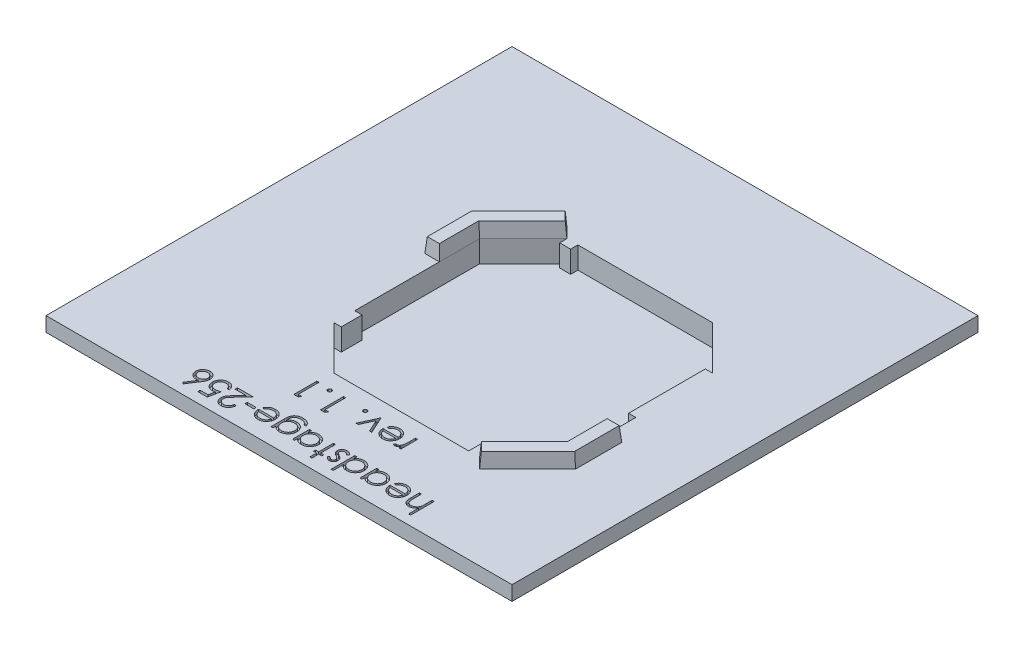
SolidWorks part; units mm, degrees
ref_plane "Front Plane" through (0, 0, 0) normal (0, 0, 1) x (1, 0, 0)
ref_plane "Top Plane" through (0, 0, 0) normal (0, 1, 0) x (1, 0, 0)
ref_plane "Right Plane" through (0, 0, 0) normal (1, 0, 0) x (0, 0, -1)
sketch "Sketch1" plane through (0, 0, 0) normal (0, 1, 0) x (1, 0, 0)
  line L1 (-32, 32) -> (32, 32)
  line L2 (-32, 32) -> (-32, -32)
  line L3 (-32, -32) -> (32, -32)
  line L4 (32, 32) -> (32, -32)
  line L5 (-32, 32) -> (32, -32) construction
  line L6 (-32, -32) -> (32, 32) construction
  point P0 (0, 0)
  dimension "D1" = 64
  dimension "D2" = 64
extrude "Boss-Extrude1" add sketch "Sketch1" along normal blind 4 contours L2 L3 L4 L1
sketch "Sketch2" plane through (0, 0, 0) normal (0, -1, 0) x (1, 0, 0)
  line L1 (-30, 30) -> (30, 30)
  line L2 (-30, 30) -> (-30, -30)
  line L3 (-30, -30) -> (30, -30)
  line L4 (30, 30) -> (30, -30)
  line L5 (-30, 30) -> (30, -30) construction
  line L6 (-30, -30) -> (30, 30) construction
  line L7 (32, 32) -> (-32, 32)
  line L8 (32, 32) -> (32, -32)
  line L9 (32, -32) -> (-32, -32)
  line L10 (-32, 32) -> (-32, -32)
  line L11 (32, 32) -> (-32, -32) construction
  line L12 (32, -32) -> (-32, 32) construction
  point P0 (0, 0)
  point P6 (0, 0)
  line M5 (-32, -32) -> (32, -32)
  line M6 (32, -32) -> (32, 32)
  line M7 (32, 32) -> (-32, 32)
  line M8 (-32, 32) -> (-32, -32)
  dimension "D1" = 2
  dimension "D2" = 2
extrude "Cut-Extrude1" cut sketch "Sketch2" against normal blind 2 contours L1 L4 L3 L2 M8 M5 M6 M7 region at (31.0949, 0, 0)
sketch "Sketch3" plane through (0, 4, 0) normal (0, 1, 0) x (1, 0, 0)
  line L0 (20.62, -13.07) -> (14.62, -19.07)
  line L2 (-11.38, 6.93) -> (-11.38, -13.07)
  line L4 (20.62, 6.93) -> (20.62, -13.07)
  line L5 (-11.38, 6.93) -> (20.62, -13.07) construction
  line L6 (-11.38, -13.07) -> (20.62, 6.93) construction
  line L7 (14.62, -19.07) -> (-5.38, -19.07)
  line L9 (14.62, 12.93) -> (-5.38, 12.93)
  line L11 (14.62, -19.07) -> (-5.38, 12.93) construction
  line L12 (14.62, 12.93) -> (-5.38, -19.07) construction
  line L13 (-11.38, -13.07) -> (-5.38, -19.07)
  line L14 (-5.38, 12.93) -> (-11.38, 6.93)
  line L15 (14.62, 12.93) -> (20.62, 6.93)
  point P0 (4.62, -3.07)
  point P1 (4.62, -3.07)
  point P5 (4.62, -3.07)
  dimension "D1" = 16
  dimension "D2" = 8.4853
  dimension "D3" = 16
extrude "Cut-Extrude2" cut sketch "Sketch3" against normal blind 3
sketch "Sketch4" plane through (0, 4, 0) normal (0, 1, 0) x (1, 0, 0)
  line L0 (20.62, -13.07) -> (20.62, 6.93) construction
  line L1 (14.62, -19.07) -> (13.12, -19.07)
  line L2 (14.62, -19.07) -> (14.62, -17.57)
  line L3 (14.62, -17.57) -> (13.12, -17.57)
  line L4 (13.12, -19.07) -> (13.12, -17.57)
  line L5 (20.62, -3.6127) -> (19.62, -3.6127)
  line L6 (20.62, -3.6127) -> (20.62, 6.93)
  line L7 (20.62, 6.93) -> (19.62, 6.93)
  line L8 (19.62, -3.6127) -> (19.62, 6.93)
  line L10 (-11.38, -13.07) -> (-10.38, -13.07)
  line L11 (-11.38, -13.07) -> (-11.38, -10.214)
  line L12 (-11.38, -10.214) -> (-10.38, -10.214)
  line L13 (-10.38, -13.07) -> (-10.38, -10.214)
  line L14 (-5.38, 12.93) -> (-3.88, 12.93)
  line L15 (-5.38, 12.93) -> (-5.38, 11.93)
  line L16 (-5.38, 11.93) -> (-3.88, 11.93)
  line L17 (-3.88, 12.93) -> (-3.88, 11.93)
  dimension "D1" = 1.5
  dimension "D2" = 1
  dimension "D3" = 1.5
  dimension "D4" = 1.5
  dimension "D5" = 1
  dimension "D6" = 1
extrude "Boss-Extrude2" add sketch "Sketch4" against normal up to surface (3 mm away) up to face at (4.62, 1, 3.07)
sketch "Sketch5" plane through (0, 4, 0) normal (0, 1, 0) x (1, 0, 0)
  line L0 (20.62, -7.5423) -> (22.62, -7.5423)
  line L1 (20.62, -13.07) -> (20.62, -3.6127) construction
  line L2 (22.62, -7.5423) -> (22.62, -13.8984)
  line L3 (22.62, -13.8984) -> (16.0342, -20.4842)
  line L4 (16.0342, -20.4842) -> (14.62, -19.07)
  line L5 (14.62, -19.07) -> (20.62, -13.07)
  line L6 (20.62, -13.07) -> (20.62, -7.5423)
  dimension "D1" = 2
  dimension "D2" = 2
extrude "Boss-Extrude3" add sketch "Sketch5" along normal blind 2 draft 5
ref_axis "Axis1" through (4.62, 4, 3.07) along (0, 1, 0)
pattern_circular "CirPattern1" count 2 over 360 about axis through (4.62, 4, 3.07) along (0, 1, 0) of "Boss-Extrude3"
sketch "Sketch6" plane through (0, 4, 0) normal (0, 1, 0) x (1, 0, 0)
  line L0 (22.7439, -27.4404) -> (-20.9196, -27.4404) construction
  text T0 "headstage-256\r\nrev. 1.1"
  point P3 (21.6403, -26.0376)
  point P4 (22.7439, -27.4404)
extrude "Cut-Extrude3" cut sketch "Sketch6" against normal blind 0.5
